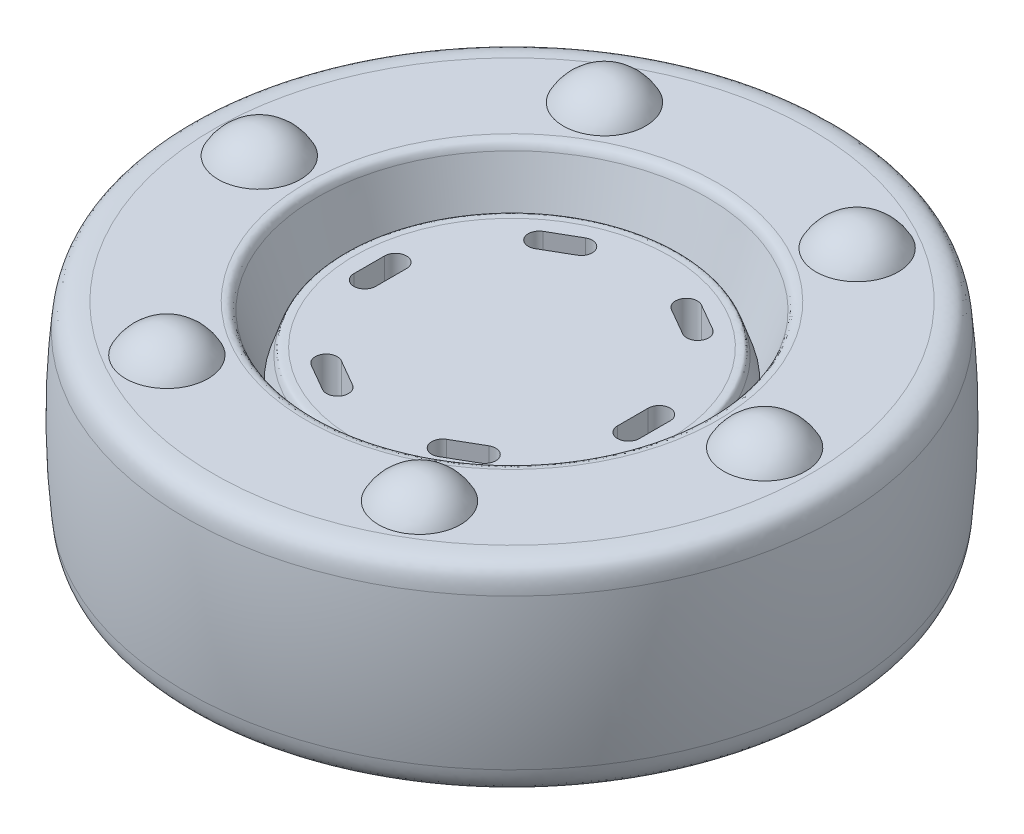
SolidWorks part; units mm, degrees
ref_plane "Front Plane" through (0, 0, 0) normal (0, 0, 1) x (1, 0, 0)
ref_plane "Top Plane" through (0, 0, 0) normal (0, 1, 0) x (1, 0, 0)
ref_plane "Right Plane" through (0, 0, 0) normal (1, 0, 0) x (0, 0, -1)
sketch "Sketch1" plane through (0, 0, 0) normal (0, 0, 1) x (1, 0, 0)
  line L0 (0, 6.985) -> (19.177, 6.985)
  line L1 (19.177, 6.985) -> (20.2476, 3.81)
  line L2 (20.2476, 3.81) -> (22.86, 11.557)
  line L3 (22.86, 11.557) -> (37.338, 11.557)
  line L4 (19.177, 6.985) -> (21.3183, 6.985) construction
  line L5 (20.2476, 6.985) -> (20.2476, 3.81) construction
  line L6 (0, 0) -> (38.1, 0)
  line L7 (0, 0) -> (0, 6.985)
  arc A0 (37.338, 11.557) -> (38.1, 0) centre (-49.9216, 0) cw
  dimension "D1" = 11.557
  dimension "D2" = 4.572
  dimension "D3" = 22.86
  dimension "D4" = 37.338
  dimension "D5" = 19.177
  dimension "D6" = 3.81
  dimension "D7" = 38.1
revolve "Revolve1" add sketch "Sketch1" angle 360 about L7
fillet "Fillet1" radius 3.175 1 edges at (0, 11.557, -37.338) conic rho 0.6
sketch "Sketch2" plane through (0, 0, 0) normal (0, 0, 1) x (1, 0, 0)
  line L0 (29.21, 14.478) -> (29.21, 3.81)
  circle A0 centre (29.21, 9.144) radius 5.334
  dimension "D2" = 10.668
  dimension "D1" = 14.478
  dimension "D3" = 29.21
revolve "Revolve4" add sketch "Sketch2" angle 360 about L0 region at (31.4738, 9.144, 0)
fillet "Fillet2" radius 1.27 1 edges at (0, 11.557, -22.86) conic rho 0.6
sketch "Sketch3" plane through (0, 6.985, 0) normal (0, 1, 0) x (1, 0, 0)
  line L0 (15.24, 1.778) -> (15.24, -1.778) construction
  line L1 (16.51, 1.778) -> (16.51, -1.778)
  line L2 (13.97, 1.778) -> (13.97, -1.778)
  arc A0 (16.51, 1.778) -> (13.97, 1.778) centre (15.24, 1.778) ccw
  arc A1 (13.97, -1.778) -> (16.51, -1.778) centre (15.24, -1.778) ccw
  point P2 (15.24, 0)
  point P7 (15.24, 3.048)
  point P8 (15.24, -3.048)
  dimension "D1" = 13.97
  dimension "D2" = 16.51
  dimension "D3" = 6.096
extrude "Cut-Extrude1" cut sketch "Sketch3" against normal through all
fillet "Fillet3" radius 1.27 1 edges at (0, 6.985, -19.177) conic rho 0.8
pattern_circular "CirPattern1" count 6 over 360 about axis through (0, 0, 0) along (0, 1, 0) of "Cut-Extrude1", "Revolve4"
mirror "Mirror1" about plane through (0, 0, 0) normal (0, 1, 0) of bodies 106
